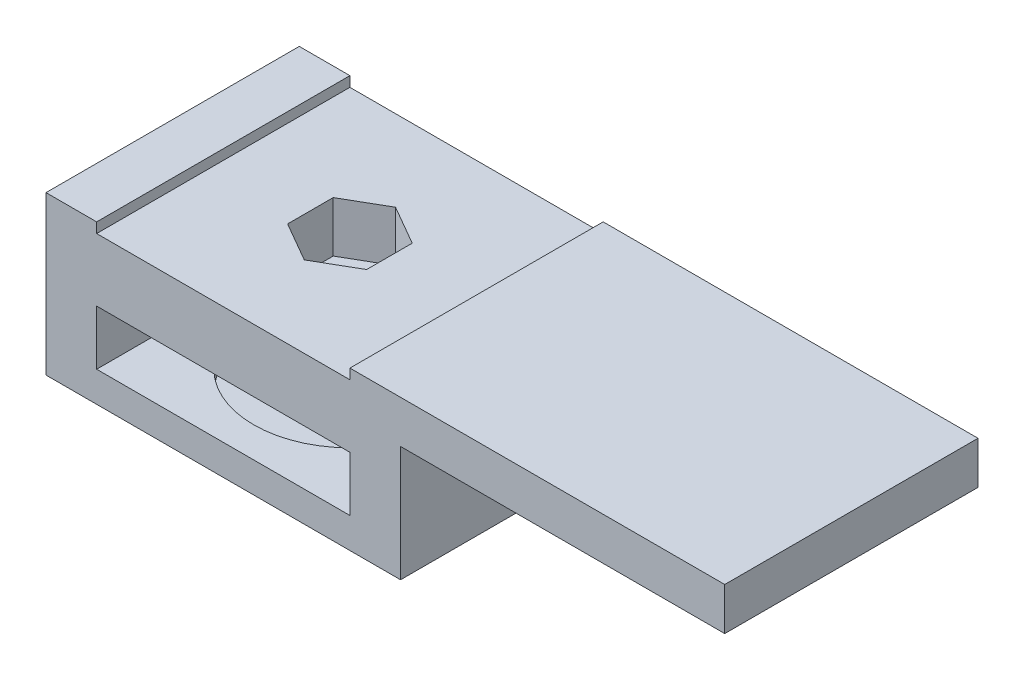
SolidWorks part; units mm, degrees
ref_plane "Front Plane" through (0, 0, 0) normal (0, 0, 1) x (1, 0, 0)
ref_plane "Top Plane" through (0, 0, 0) normal (0, 1, 0) x (1, 0, 0)
ref_plane "Right Plane" through (0, 0, 0) normal (1, 0, 0) x (0, 0, -1)
sketch "Sketch1" plane through (0, 0, 0) normal (0, 1, 0) x (1, 0, 0)
  line L1 (-12.5, -12.5) -> (12.5, -12.5)
  line L2 (-12.5, -12.5) -> (-12.5, 12.5)
  line L3 (-12.5, 12.5) -> (12.5, 12.5)
  line L4 (12.5, -12.5) -> (12.5, 12.5)
  line L5 (-12.5, -12.5) -> (12.5, 12.5) construction
  line L6 (-12.5, 12.5) -> (12.5, -12.5) construction
  circle A0 centre (0, 0) radius 9.5
  dimension "D1" = 19
  dimension "D2" = 25
extrude "alongside washer" add sketch "Sketch1" along normal blind 2
sketch "Sketch2" plane through (0, 0, 0) normal (0, -1, 0) x (1, 0, 0)
  line L0 (12.5, 12.5) -> (12.5, -12.5) construction
  line L1 (12.5, -12.5) -> (-12.5, -12.5) construction
  line L2 (-12.5, -12.5) -> (-12.5, 12.5) construction
  line L3 (-12.5, 12.5) -> (12.5, 12.5) construction
  line L4 (12.5, 12.5) -> (12.5, -12.5)
  line L5 (12.5, -12.5) -> (-12.5, -12.5)
  line L6 (-12.5, -12.5) -> (-12.5, 12.5)
  line L7 (-12.5, 12.5) -> (12.5, 12.5)
extrude "below washer" add sketch "Sketch2" along normal blind 1
sketch "Sketch3" plane through (0, -1, 0) normal (0, -1, 0) x (1, 0, 0)
  line L1 (-12.5, -12.5) -> (-17.5, -12.5)
  line L2 (-12.5, -12.5) -> (-12.5, 12.5)
  line L3 (-12.5, 12.5) -> (-17.5, 12.5)
  line L4 (-17.5, -12.5) -> (-17.5, 12.5)
  dimension "D1" = 5
extrude "upright 1" add sketch "Sketch3" against normal blind 15.6
sketch "Sketch4" plane through (-12.5, 0, 0) normal (1, 0, 0) x (0, 0, -1)
  line L0 (-12.5, 14.6) -> (-12.5, 2) construction
  line L1 (-12.5, 7.4) -> (12.5, 7.4)
  line L2 (-12.5, 7.4) -> (-12.5, 8.6)
  line L3 (-12.5, 8.6) -> (12.5, 8.6)
  line L4 (12.5, 7.4) -> (12.5, 8.6)
  line L5 (12.5, 14.6) -> (12.5, 2) construction
  line L6 (-12.5, 2) -> (12.5, 2) construction
  dimension "D1" = 5.4
  dimension "D2" = 1.2
extrude "Boss-Extrude4" add sketch "Sketch4" along normal up to surface (25 mm away) up to face at (12.5, 0.5, 0)
sketch "Sketch5" plane through (0, 8.6, 0) normal (0, 1, 0) x (1, 0, 0)
  circle A0 centre (0, 0) radius 2.75
  dimension "D1" = 5.5
extrude "Cut-Extrude1" cut sketch "Sketch5" against normal up to surface (1.2 mm away) up to face at (0, 7.4, 0)
sketch "Sketch6" plane through (0, 8.6, 0) normal (0, 1, 0) x (1, 0, 0)
  line L0 (12.5, 12.5) -> (-12.5, 12.5) construction
  line L1 (3.9, 2.2517) -> (0, 4.5033)
  line L2 (0, 4.5033) -> (-3.9, 2.2517)
  line L3 (-3.9, 2.2517) -> (-3.9, -2.2517)
  line L4 (-3.9, -2.2517) -> (0, -4.5033)
  line L5 (0, -4.5033) -> (3.9, -2.2517)
  line L6 (3.9, -2.2517) -> (3.9, 2.2517)
  line L7 (-12.5, 12.5) -> (12.5, 12.5)
  line L9 (-12.5, -12.5) -> (12.5, -12.5)
  line L10 (12.5, 12.5) -> (12.5, -12.5)
  line L11 (12.5, -12.5) -> (-12.5, -12.5) construction
  line L12 (-12.5, 12.5) -> (-12.5, -12.5) construction
  line L13 (-12.5, 12.5) -> (-12.5, -12.5) construction
  line L14 (-12.5, 12.5) -> (-12.5, -12.5)
  circle A0 centre (0, 0) radius 3.9 construction
  point P17 (0, 12.5)
  dimension "D1" = 7.8
extrude "Boss-Extrude5" add sketch "Sketch6" along normal blind 6.2 from surface starting at face at (0, 7.4, 2.75)
mirror "Mirror1" about plane through (0, 0, 0) normal (1, 0, 0) of "upright 1"
sketch "Sketch7" plane through (17.5, 0, 0) normal (1, 0, 0) x (0, 0, -1)
  line L1 (-12.5, -1) -> (12.5, -1) construction
  circle A0 centre (0, 5.2) radius 3.1
  dimension "D1" = 6.2
  dimension "D2" = 6.2
extrude "Cut-Extrude2" cut sketch "Sketch7" against normal through all
sketch "Sketch8" plane through (12.5, 0, 0) normal (1, 0, 0) x (0, 0, -1)
  line L1 (-12.5, 14.6) -> (12.5, 14.6)
  line L2 (-12.5, 14.6) -> (-12.5, 10.4)
  line L3 (-12.5, 10.4) -> (12.5, 10.4)
  line L4 (12.5, 14.6) -> (12.5, 10.4)
  line L5 (12.5, 14.6) -> (12.5, -1) construction
  dimension "D1" = 4.2
  dimension "D2" = 25
extrude "Boss-Extrude6" add sketch "Sketch8" along normal blind 37
sketch "Sketch9" plane through (12.5, 0, 0) normal (-1, 0, 0) x (0, 0, 1)
  circle A0 centre (0, 5.2) radius 1
  circle A1 centre (0, 5.2) radius 3.1 construction
  circle A2 centre (0, 5.2) radius 3.1
  arc M2 (2.184, 7.4) -> (-2.184, 7.4) centre (0, 5.2) cw
  dimension "D1" = 2
extrude "Boss-Extrude7" add sketch "Sketch9" against normal blind 1 contours A2 A0 M2 region at (12.5, 2.4191, -1.1578)
mirror "Mirror2" [suppressed] about plane through (0, 0, 0) normal (1, 0, 0)
sketch "Sketch10" plane through (0, 8.6, 0) normal (0, 1, 0) x (1, 0, 0)
  line L4 (0, -4.5033) -> (3.9, -2.2517)
  line L18 (0, -4.5033) -> (3.9, -2.2517)
  line L20 (3.9, -2.2517) -> (3.9, 2.2517)
  line L24 (3.9, -2.2517) -> (3.9, 2.2517)
  line L30 (3.9, 2.2517) -> (0, 4.5033)
  line L31 (3.9, 2.2517) -> (0, 4.5033)
  line L32 (0, 4.5033) -> (-3.9, 2.2517)
  line L33 (0, 4.5033) -> (-3.9, 2.2517)
  line L34 (-3.9, 2.2517) -> (-3.9, -2.2517)
  line L35 (-3.9, 2.2517) -> (-3.9, -2.2517)
  line L36 (-3.9, -2.2517) -> (0, -4.5033)
  line L37 (-3.9, -2.2517) -> (0, -4.5033)
  circle A0 centre (0, 0) radius 2.75 construction
  circle A1 centre (0, 0) radius 2.75
  dimension "D1" = 0
extrude "Boss-Extrude8" [suppressed] add sketch "Sketch10" along normal up to surface (2.2 mm away) from offset 3.8
sketch "Sketch12" [suppressed] plane through (0, 0, 12.5) normal (0, 0, 1) x (1, 0, 0)
  line L0 (-3.95, 12.9) -> (3.95, 12.9)
  line L1 (-3.85, 9.2) -> (3.85, 9.2) construction
  line L2 (-3.85, 9.2) -> (-3.85, 12.8) construction
  line L3 (-3.85, 12.8) -> (3.85, 12.8) construction
  line L4 (3.85, 9.2) -> (3.85, 12.8) construction
  line L5 (3.95, 9.1) -> (3.95, 12.9)
  line L6 (-3.95, 9.1) -> (3.95, 9.1)
  line L7 (-3.95, 9.1) -> (-3.95, 12.9)
  line L8 (-3.85, 11) -> (3.95, 11) construction
  line L9 (-12.5, 14.6) -> (-17.5, 14.6) construction
  line L10 (12.5, 7.4) -> (-12.5, 7.4) construction
  line L18 (0, 12.0819) -> (0, 10.1098) construction
  line L26 (-12.5, 7.4) -> (-12.5, 2) construction
  line L27 (0, 13.6) -> (0, 8.6) construction
  line L38 (12.5, 7.4) -> (12.5, 2) construction
  dimension "D1" = 0.1
  dimension "D2" = 3.8
  dimension "D3" = 7.8
extrude "Cut-Extrude3" [suppressed] cut sketch "Sketch12" against normal up to vertex
chamfer "Chamfer1" [suppressed] distance 0.1 angle 45
sketch "Sketch14" [suppressed] plane through (0, 13.4, 0) normal (0, 1, 0) x (1, 0, 0)
  line L0 (-17.5, 12.5) -> (49.5, 12.5) construction
  line L1 (49.5, 12.5) -> (49.5, -12.5) construction
  point P0 (29.36, 6.66)
  point P1 (29.36, -3.84)
  dimension "D1" = 10.5
  dimension "D2" = 5.84
  dimension "D3" = 20.14
sketch "Sketch15" [suppressed] plane through (0, 8.4, 0) normal (0, -1, 0) x (1, 0, 0)
  line L1 (30.9766, 6.64) -> (27.7434, 6.64)
  line L2 (27.7434, 6.64) -> (26.1268, 3.84)
  line L3 (26.1268, 3.84) -> (27.7434, 1.04)
  line L4 (27.7434, 1.04) -> (30.9766, 1.04)
  line L5 (30.9766, 1.04) -> (32.5932, 3.84)
  line L6 (32.5932, 3.84) -> (30.9766, 6.64)
  line L7 (30.9766, -3.86) -> (27.7434, -3.86)
  line L8 (27.7434, -3.86) -> (26.1268, -6.66)
  line L9 (26.1268, -6.66) -> (27.7434, -9.46)
  line L10 (27.7434, -9.46) -> (30.9766, -9.46)
  line L11 (30.9766, -9.46) -> (32.5932, -6.66)
  line L12 (32.5932, -6.66) -> (30.9766, -3.86)
  circle A0 centre (29.36, 3.84) radius 2.8 construction
  circle A1 centre (29.36, -6.66) radius 2.8 construction
  dimension "D1" = 5.6
extrude "Cut-Extrude4" [suppressed] cut sketch "Sketch15" against normal blind 2.4
